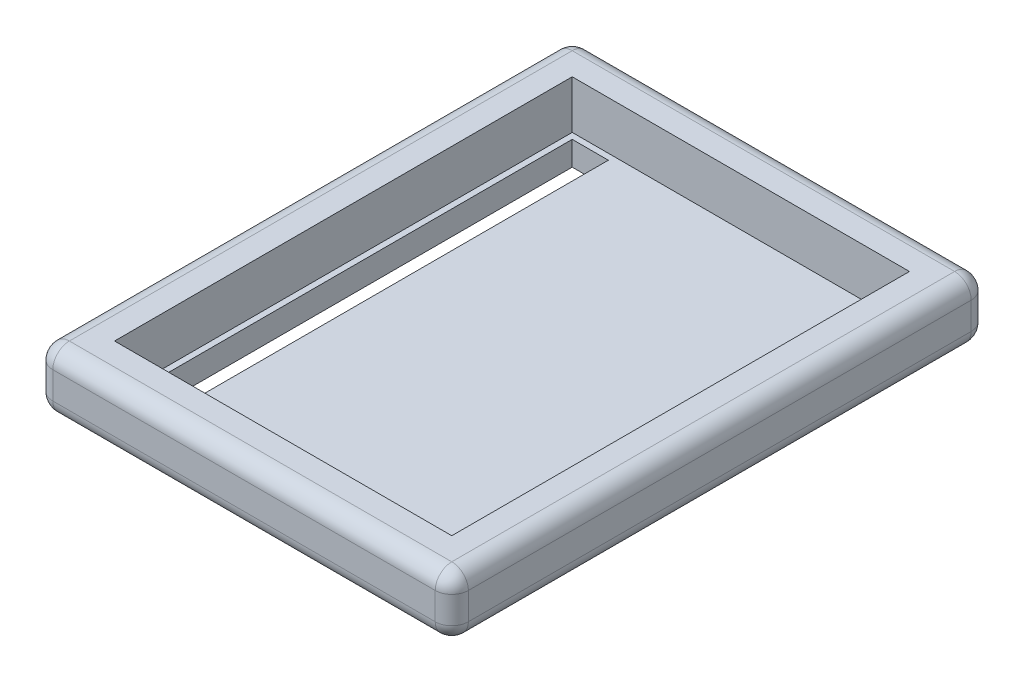
SolidWorks part; units mm, degrees
ref_plane "Front Plane" through (0, 0, 0) normal (0, 0, 1) x (1, 0, 0)
ref_plane "Top Plane" through (0, 0, 0) normal (0, 1, 0) x (1, 0, 0)
ref_plane "Right Plane" through (0, 0, 0) normal (1, 0, 0) x (0, 0, -1)
sketch "Sketch1" plane through (0, 0, 0) normal (0, 1, 0) x (1, 0, 0)
  line L0 (-355.6, 0) -> (0, 0) construction
  line L1 (-355.6, -482.6) -> (355.6, -482.6)
  line L2 (-355.6, -482.6) -> (-355.6, 482.6)
  line L3 (-355.6, 482.6) -> (355.6, 482.6)
  line L4 (355.6, -482.6) -> (355.6, 482.6)
  line L5 (0, 0) -> (355.6, 0) construction
  line L6 (0, 0) -> (0, 482.6) construction
  line L7 (0, 0) -> (0, -482.6) construction
  line L9 (-342.9, 469.9) -> (-266.7, 469.9)
  line L10 (-342.9, 469.9) -> (-342.9, -469.9)
  line L11 (-342.9, -469.9) -> (-266.7, -469.9)
  line L12 (-266.7, 469.9) -> (-266.7, -469.9)
  line L13 (342.9, 469.9) -> (266.7, 469.9)
  line L14 (342.9, 469.9) -> (342.9, -469.9)
  line L15 (342.9, -469.9) -> (266.7, -469.9)
  line L16 (266.7, 469.9) -> (266.7, -469.9)
  dimension "D1" = 711.2
  dimension "D2" = 965.2
  dimension "D3" = 12.7
  dimension "D4" = 12.7
  dimension "D5" = 12.7
  dimension "D6" = 12.7
  dimension "D7" = 12.7
  dimension "D8" = 12.7
  dimension "D9" = 76.2
  dimension "D10" = 76.2
extrude "Boss-Extrude1" add sketch "Sketch1" along normal blind 50.8
sketch "Sketch2" plane through (0, 0, 482.6) normal (0, 0, 1) x (1, 0, 0)
  line L0 (-355.6, 0) -> (355.6, 0) construction
  line L1 (-355.6, 25.4) -> (355.6, 25.4)
  line L2 (-355.6, 25.4) -> (-355.6, 152.4)
  line L3 (-355.6, 152.4) -> (355.6, 152.4)
  line L4 (355.6, 25.4) -> (355.6, 152.4)
  line L5 (-355.6, 50.8) -> (-355.6, 0) construction
  line L6 (355.6, 50.8) -> (355.6, 0) construction
  dimension "D1" = 127
  dimension "D2" = 25.4
extrude "Boss-Extrude2" add sketch "Sketch2" along normal blind 82.55
sketch "Sketch3" plane through (0, 0, -482.6) normal (0, 0, -1) x (-1, 0, 0)
  line L0 (-355.6, 50.8) -> (-355.6, 0) construction
  line L1 (-355.6, 25.4) -> (355.6, 25.4)
  line L2 (-355.6, 25.4) -> (-355.6, 152.4)
  line L3 (-355.6, 152.4) -> (355.6, 152.4)
  line L4 (355.6, 25.4) -> (355.6, 152.4)
  line L5 (355.6, 50.8) -> (355.6, 0) construction
  line L6 (-355.6, 0) -> (355.6, 0) construction
  dimension "D1" = 127
  dimension "D2" = 25.4
extrude "Boss-Extrude3" add sketch "Sketch3" along normal blind 82.55
sketch "Sketch4" plane through (355.6, 0, 0) normal (1, 0, 0) x (0, 0, -1)
  line L1 (-565.15, 25.4) -> (565.15, 25.4)
  line L2 (-565.15, 25.4) -> (-565.15, 152.4)
  line L3 (-565.15, 152.4) -> (565.15, 152.4)
  line L4 (565.15, 25.4) -> (565.15, 152.4)
extrude "Boss-Extrude4" add sketch "Sketch4" along normal blind 82.55
sketch "Sketch5" plane through (-355.6, 0, 0) normal (-1, 0, 0) x (0, 0, 1)
  line L1 (-565.15, 25.4) -> (565.15, 25.4)
  line L2 (-565.15, 25.4) -> (-565.15, 152.4)
  line L3 (-565.15, 152.4) -> (565.15, 152.4)
  line L4 (565.15, 25.4) -> (565.15, 152.4)
extrude "Boss-Extrude5" add sketch "Sketch5" along normal blind 82.55
fillet "Fillet1" radius 34.925 12 edges at (-438.15, 88.9, 565.15) (-438.15, 88.9, -565.15) (438.15, 88.9, -565.15) (438.15, 88.9, 565.15) (0, 25.4, 565.15) (438.15, 25.4, 0) (0, 25.4, -565.15) (-438.15, 25.4, 0) (-438.15, 152.4, 0) (0, 152.4, 565.15) (438.15, 152.4, 0) (0, 152.4, -565.15)
